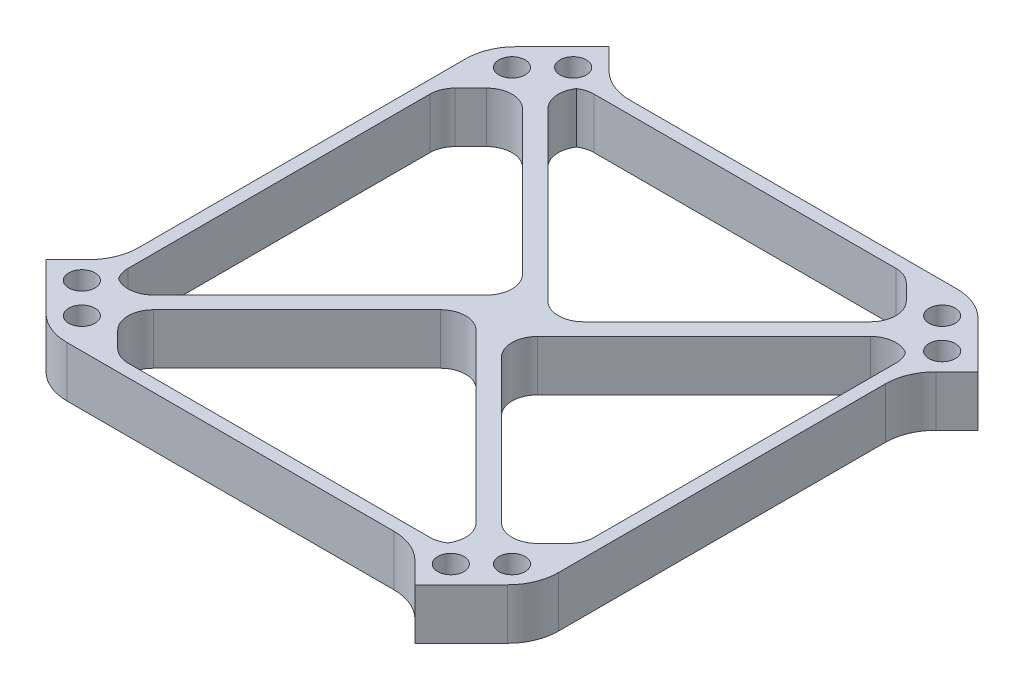
SolidWorks part; units mm, degrees
ref_plane "Front Plane" through (0, 0, 0) normal (0, 0, 1) x (1, 0, 0)
ref_plane "Top Plane" through (0, 0, 0) normal (0, 1, 0) x (1, 0, 0)
ref_plane "Right Plane" through (0, 0, 0) normal (1, 0, 0) x (0, 0, -1)
sketch "Sketch1" plane through (0, 0, 0) normal (0, 1, 0) x (1, 0, 0)
  line L0 (-55.533, 36.3909) -> (-36.3909, 55.533) construction
  line L1 (-36.3909, 55.533) -> (36.3909, 55.533) construction
  line L2 (36.3909, 55.533) -> (55.533, 36.3909) construction
  line L3 (55.533, 36.3909) -> (55.533, -36.3909) construction
  line L4 (55.533, -36.3909) -> (36.3909, -55.533) construction
  line L5 (36.3909, -55.533) -> (-36.3909, -55.533) construction
  line L6 (-36.3909, -55.533) -> (-55.533, -36.3909) construction
  line L7 (-55.533, -36.3909) -> (-55.533, 36.3909) construction
  line L8 (0, 0) -> (0, 31.0491) construction
  line L9 (0, 0) -> (32.6609, 0) construction
  line L10 (-48.4619, 43.4619) -> (-36.3909, 55.533)
  line L11 (-45.9619, -45.9619) -> (45.9619, -45.9619) construction
  line L12 (-45.9619, -45.9619) -> (-45.9619, 45.9619) construction
  line L13 (-45.9619, 45.9619) -> (45.9619, 45.9619) construction
  line L14 (45.9619, -45.9619) -> (45.9619, 45.9619) construction
  line L15 (-36.3909, 55.533) -> (-29.3198, 48.4619)
  line L16 (-29.3198, 48.4619) -> (43.4619, 48.4619)
  line L17 (43.4619, 48.4619) -> (55.533, 36.3909)
  line L18 (55.533, 36.3909) -> (48.4619, 29.3198)
  line L19 (48.4619, 29.3198) -> (48.4619, -43.4619)
  line L20 (48.4619, -43.4619) -> (36.3909, -55.533)
  line L21 (36.3909, -55.533) -> (29.3198, -48.4619)
  line L22 (29.3198, -48.4619) -> (-43.4619, -48.4619)
  line L23 (-43.4619, -48.4619) -> (-55.533, -36.3909)
  line L24 (-55.533, -36.3909) -> (-48.4619, -29.3198)
  line L25 (-48.4619, -29.3198) -> (-48.4619, 43.4619)
  point P18 (-45.9619, 45.9619)
  dimension "D1" = 65
  dimension "D2" = 10
  dimension "D3" = 2.5
extrude "Boss-Extrude1" add sketch "Sketch1" along normal blind 10
sketch "Sketch2" plane through (0, 10, 0) normal (0, 1, 0) x (1, 0, 0)
  line L0 (0, 0) -> (0, 27.7289) construction
  line L1 (48.4619, -48.4619) -> (-48.4619, -48.4619) construction
  line L2 (-48.4619, 43.4619) -> (-48.4619, -29.3198) construction
  line L3 (48.4619, 48.4619) -> (-48.4619, 48.4619) construction
  line L4 (-48.4619, -48.4619) -> (-48.4619, 48.4619) construction
  line L5 (0, 0) -> (26.129, 0) construction
  line L10 (-2.5, 4.5711) -> (-42.4264, -35.3553)
  line L11 (-45.9619, 31.8198) -> (-37.8553, 39.9264)
  line L12 (-37.8553, 39.9264) -> (-2.5, 4.5711)
  line L13 (-42.4264, -35.3553) -> (-45.9619, -31.8198)
  line L15 (43.4619, 48.4619) -> (-29.3198, 48.4619) construction
  line L16 (-43.4619, -48.4619) -> (29.3198, -48.4619) construction
  line L17 (48.4619, 48.4619) -> (48.4619, -48.4619) construction
  line L18 (48.4619, -43.4619) -> (48.4619, 29.3198) construction
  line L19 (-36.3909, 55.533) -> (-48.4619, 43.4619) construction
  line L20 (-45.9619, -31.8198) -> (-45.9619, 31.8198)
  line L21 (-48.4619, -29.3198) -> (-45.9619, -31.8198) construction
  dimension "D1" = 10
  dimension "D2" = 5
  dimension "D3" = 5
  dimension "D4" = 2.5
extrude "Cut-Extrude1" cut sketch "Sketch2" against normal through all
ref_axis "Axis2" through (0, 10.5, 0) along (0, -1, 0)
fillet "Fillet4" radius 5 5 edges at (-37.8553, 5, -39.9264) (-2.5, 5, -4.5711) (-45.9619, 5, 31.8198) (-42.4264, 5, 35.3553) (-45.9619, 5, -31.8198)
pattern_circular "CirPattern6" count 4 over 360 about axis through (0, 10.5, 0) along (0, -1, 0) of "Cut-Extrude1", "Fillet4"
fillet "Fillet5" radius 10 8 edges at (43.4619, 5, -48.4619) (-29.3198, 5, -48.4619) (-48.4619, 5, -43.4619) (-48.4619, 5, 29.3198) (-43.4619, 5, 48.4619) (29.3198, 5, 48.4619) (48.4619, 5, -29.3198) (48.4619, 5, 43.4619)
hole_wizard "#6 (0.204) Diameter Hole1" positions "Sketch3" profile "Sketch4" hole size "#6" standard "ANSI Inch" end condition through all
sketch "Sketch3" plane through (0, 10, 0) normal (0, 1, 0) x (1, 0, 0)
  line L1 (42.4264, -42.4264) -> (-42.4264, -42.4264) construction
  line L2 (42.4264, -42.4264) -> (42.4264, 42.4264) construction
  line L3 (42.4264, 42.4264) -> (-42.4264, 42.4264) construction
  line L4 (-42.4264, -42.4264) -> (-42.4264, 42.4264) construction
  line L5 (0, 0) -> (0, 27.9091) construction
  line L7 (0, 0) -> (26.5726, 0) construction
  line L9 (-36.3909, 55.533) -> (-45.533, 46.3909) construction
  line L11 (-43.4619, 48.4619) -> (-36.3909, 55.533) construction
  line L12 (-43.4619, 48.4619) -> (-36.3909, 41.3909) construction
  line L13 (-36.3909, 55.533) -> (-29.3198, 48.4619) construction
  line L16 (-36.3909, 41.3909) -> (-36.3909, 55.533) construction
  line L18 (-43.4619, 48.4619) -> (-29.3198, 48.4619) construction
  line L20 (-29.3198, 48.4619) -> (-36.3909, 41.3909) construction
  line L22 (-41.3909, 36.3909) -> (-44.4975, 33.2843) construction
  point P3 (-42.4264, 42.4264)
  point P355 (-36.3909, 48.4619)
  dimension "D1" = 5
  dimension "D2" = 60
sketch "Sketch4" plane through (-42.4264, 10, -42.4264) normal (1, 0, 0) x (0, 0, 1)
  line L0 (0, 0) -> (0, 10)
  line L1 (0, 10) -> (2.5908, 10)
  line L2 (2.5908, 10) -> (2.5908, 0)
  line L5 (2.5908, 0) -> (0, 0)
  line L11 (0, -6.35) -> (0, 107.95) construction
  dimension "Thru Hole Dia." = 5.1816
  dimension "Thru Hole Depth" = 10
pattern_circular "CirPattern7" count 4 over 360 about axis through (0, 10.5, 0) along (0, -1, 0) of "#6 (0.204) Diameter Hole1"
equation "\"TubeDiameter\"= 6.6929in"
